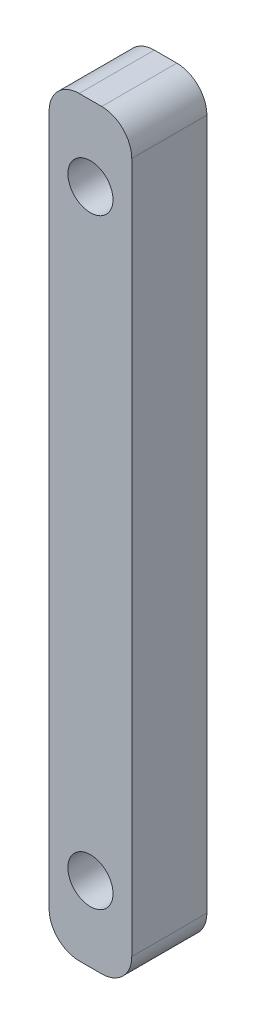
SolidWorks part; units mm, degrees
ref_plane "前视基准面" through (0, 0, 0) normal (0, 0, 1) x (1, 0, 0)
ref_plane "上视基准面" through (0, 0, 0) normal (0, 1, 0) x (1, 0, 0)
ref_plane "右视基准面" through (0, 0, 0) normal (1, 0, 0) x (0, 0, -1)
sketch "草图1" plane through (0, 0, 0) normal (0, 0, 1) x (1, 0, 0)
  line L1 (2.75, -25) -> (-2.75, -25)
  line L2 (2.75, -25) -> (2.75, 25)
  line L3 (2.75, 25) -> (-2.75, 25)
  line L4 (-2.75, -25) -> (-2.75, 25)
  line L5 (2.75, -25) -> (-2.75, 25) construction
  line L6 (2.75, 25) -> (-2.75, -25) construction
  point P0 (0, 0)
  dimension "D1" = 5.5
  dimension "D2" = 50
extrude "凸台-拉伸1" add sketch "草图1" along normal blind 5
sketch "草图2" plane through (0, 0, 5) normal (0, 0, 1) x (1, 0, 0)
  circle A0 centre (0, 20) radius 1.5
  circle A1 centre (0, -20) radius 1.5
  point P0 (0, 19.6602)
  dimension "D3" = 3
  dimension "D4" = 3
  dimension "D1" = 20
  dimension "D2" = 20
extrude "切除-拉伸1" cut sketch "草图2" against normal through all
fillet "圆角1" radius 2 4 edges at (-2.75, -25, 2.5) (2.75, -25, 2.5) (2.75, 25, 2.5) (-2.75, 25, 2.5)
